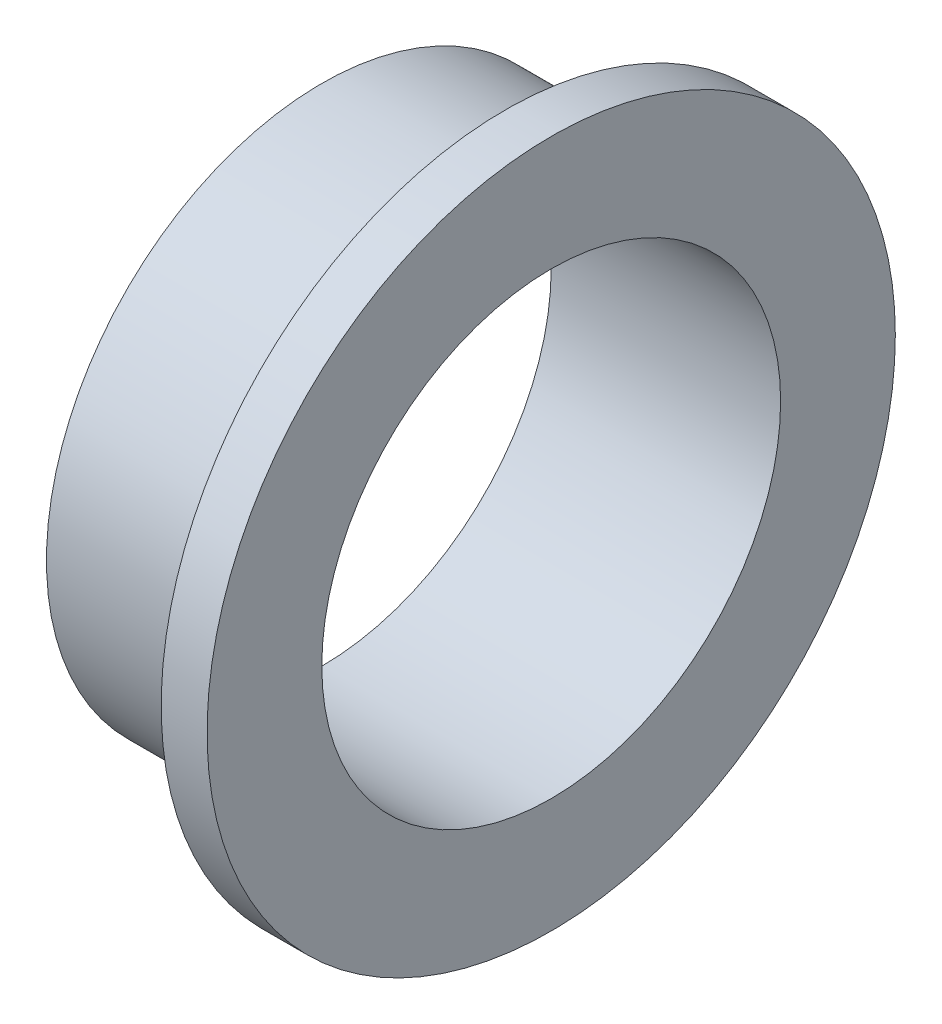
SolidWorks part; units mm, degrees
material "SAE 660 bearing bronze"
ref_plane "Front Plane" through (0, 0, 0) normal (1, 0, 0) x (0, 1, 0)
ref_plane "Top Plane" through (0, 0, 0) normal (0, 0, 1) x (0, 1, 0)
ref_plane "Right Plane" through (0, 0, 0) normal (0, 1, 0) x (-1, 0, 0)
sketch "Sketch2" plane through (0, 0, 0) normal (1, 0, 0) x (0, 1, 0)
  circle A0 centre (0, 0) radius 7.5
  circle A1 centre (0, 0) radius 6
  circle A2 centre (0, 0) radius 5
  dimension "D1" = 15
  dimension "D2" = 12
  dimension "D3" = 10
extrude "Boss-Extrude1" add sketch "Sketch2" against normal blind 1 contours A0 A1 region at (0, -7.2879, 0)
extrude "Boss-Extrude2" add sketch "Sketch2<3>" against normal blind 5 contours A1 A2 region at (0, -5.8303, 0)
sketch "Sketch2<3>" plane through (0, 0, 0) normal (1, 0, 0) x (0, 1, 0) same geometry as "Sketch2"
